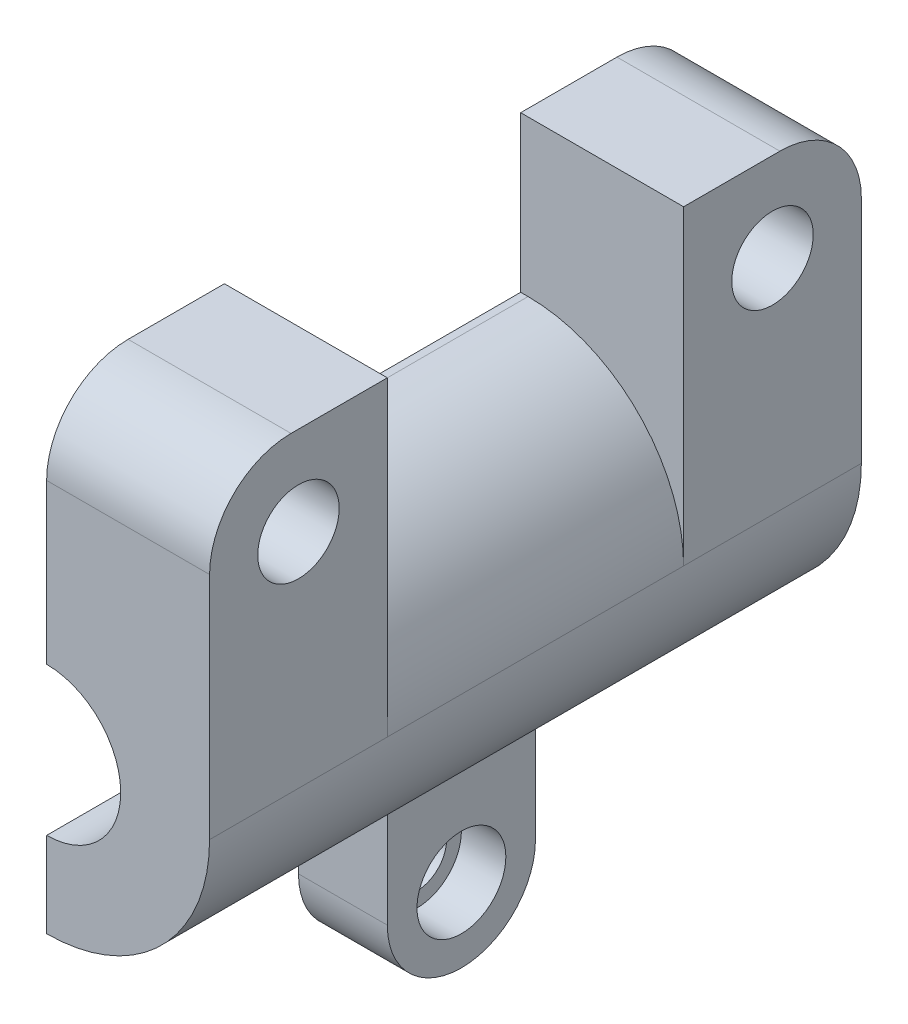
SolidWorks part; units mm, degrees
ref_plane "Front Plane" through (0, 0, 0) normal (0, 0, 1) x (1, 0, 0)
ref_plane "Top Plane" through (0, 0, 0) normal (0, 1, 0) x (1, 0, 0)
ref_plane "Right Plane" through (0, 0, 0) normal (1, 0, 0) x (0, 0, -1)
sketch "Sketch1" plane through (0, 0, 0) normal (1, 0, 0) x (0, 0, -1)
  line L1 (-22, -16) -> (22, -16)
  line L2 (-22, -16) -> (-22, 16)
  line L3 (-22, 16) -> (22, 16)
  line L4 (22, -16) -> (22, 16)
  line L5 (-22, -16) -> (22, 16) construction
  line L6 (-22, 16) -> (22, -16) construction
  point P0 (0, 0)
  dimension "D1" = 44
  dimension "D2" = 32
extrude "Boss-Extrude1" add sketch "Sketch1" along normal blind 11
sketch "Sketch2" plane through (0, 0, 0) normal (1, 0, 0) x (0, 0, -1)
  line L0 (-22, -16) -> (22, -16) construction
  line L1 (12.25, -13) -> (-12.25, -13)
  line L2 (12.25, -13) -> (12.25, 2.5)
  line L3 (12.25, 2.5) -> (-12.25, 2.5)
  line L4 (-12.25, -13) -> (-12.25, 2.5)
  line L5 (12.25, -13) -> (-12.25, 2.5) construction
  line L6 (12.25, 2.5) -> (-12.25, -13) construction
  point P0 (0, -5.25)
  dimension "D1" = 24.5
  dimension "D2" = 15.5
  dimension "D3" = 0
  dimension "D4" = 3
extrude "Cut-Extrude1" cut sketch "Sketch2" along normal blind 7.75 contours L2 L1 L4 L3
fillet "Fillet1" radius 7.75 2 edges at (7.75, 2.5, 0) (7.75, -13, 0)
sketch "Sketch3" plane through (0, 0, -12.25) normal (0, 0, 1) x (1, 0, 0)
  arc A0 (0, -13) -> (7.75, -5.25) centre (0, -5.25) ccw construction
  arc A1 (0, -13) -> (7.75, -5.25) centre (0, -5.25) ccw
  circle A2 centre (0, -5.25) radius 5
  line M3 (0, 2.5) -> (0, -13)
  dimension "D1" = 10
extrude "Cut-Extrude2" cut sketch "Sketch3" against normal through all both and the other way through all contours A2 M3 | A2 M3 region at (2.1221, -5.25, -12.25) region at (-2.1221, -5.25, -12.25)
sketch "Sketch4" plane through (11, 0, 0) normal (1, 0, 0) x (0, 0, -1)
  line L0 (22, 16) -> (-22, 16) construction
  line L2 (-10, 16) -> (10, 16)
  line L3 (-10, 16) -> (-10, 5.5)
  line L4 (-10, 5.5) -> (10, 5.5)
  line L5 (10, 16) -> (10, 5.5)
  circle A0 centre (-16, 10) radius 2.75
  circle A1 centre (16, 10) radius 2.75
  dimension "D1" = 5.5
  dimension "D2" = 5.5
  dimension "D3" = 6
  dimension "D4" = 6
  dimension "D5" = 6
  dimension "D6" = 6
  dimension "D7" = 32
  dimension "D8" = 10
  dimension "D9" = 10.5
extrude "Cut-Extrude3" cut sketch "Sketch4" against normal through all
sketch "Sketch5" plane through (11, 0, 0) normal (1, 0, 0) x (0, 0, -1)
  line L0 (-16, 10) -> (-16, 4.5)
  line L1 (-2.75, -3) -> (2.75, -3)
  line L2 (-2.75, -3) -> (-2.75, 0)
  line L3 (-2.75, 0) -> (2.75, 0)
  line L4 (2.75, -3) -> (2.75, 0)
  line L5 (-2.75, -3) -> (2.75, 0) construction
  line L6 (-2.75, 0) -> (2.75, -3) construction
  line L7 (16, 10) -> (16, 4.5)
  line L8 (-2.75, 0) -> (-16, 4.5)
  line L9 (2.75, 0) -> (16, 4.5)
  line L10 (2.75, -3) -> (16, 4.5)
  line L11 (-2.75, -3) -> (-16, 4.5)
  line L12 (16, 4.5) -> (16, -3)
  line L13 (16, -3) -> (2.75, -3)
  line L14 (-2.75, -3) -> (-16, -3)
  line L15 (-16, -3) -> (-16, 4.5)
  circle A0 centre (16, 10) radius 2.75 construction
  circle A1 centre (16, 10) radius 2.75
  circle A2 centre (-16, 10) radius 2.75 construction
  circle A3 centre (-16, 10) radius 2.75
  point P0 (0, -1.5)
  dimension "D1" = 10
  dimension "D2" = 3
  dimension "D3" = 5.5
  dimension "D4" = 0
  dimension "D5" = 5.5
  dimension "D6" = 5.5
extrude "Boss-Extrude4" [suppressed] add sketch "Sketch5" along normal blind 7 contours L15 L14 L11 | L11 L2 L8 | L1 L4 L3 L2 | L4 L10 L9 | L13 L12 L10
chamfer "Chamfer1" [suppressed] distance 7 angle 45
sketch "Sketch6" [suppressed] plane through (12, 0, 0) normal (1, 0, 0) x (0, 0, -1)
  line L0 (16, -3) -> (-16, -3) construction
  line L1 (16, -3) -> (-16, -3)
  line L2 (16, -10) -> (-16, -10) construction
  line L3 (-13, -3) -> (13, -3)
  line L4 (-13, -3) -> (-13, -10)
  line L5 (-13, -10) -> (13, -10)
  line L6 (13, -3) -> (13, -10)
  line L7 (-16, -10) -> (-16, -3) construction
  line L8 (10, 5.5) -> (-10, 5.5)
  line L9 (-10, 5.5) -> (-10, 16)
  line L10 (-10, 16) -> (-22, 16)
  line L11 (-22, 16) -> (-22, -16)
  line L12 (-22, -16) -> (22, -16)
  line L13 (22, -16) -> (22, 16)
  line L14 (22, 16) -> (10, 16)
  line L15 (10, 16) -> (10, 5.5)
  line L16 (10, 5.5) -> (-10, 5.5)
  line L17 (-10, 5.5) -> (-10, 16)
  line L18 (-10, 16) -> (-22, 16)
  line L19 (-22, 16) -> (-22, -16)
  line L20 (-22, -16) -> (22, -16)
  line L21 (22, -16) -> (22, 16)
  line L22 (22, 16) -> (10, 16)
  line L23 (10, 16) -> (10, 5.5)
  line L24 (16, 4.5) -> (16, -10) construction
  line L25 (-2.75, 0) -> (2.75, 0) construction
  line L26 (-1.5, -3) -> (1.5, -3)
  line L27 (-1.5, -3) -> (-1.5, -10)
  line L28 (-1.5, -10) -> (1.5, -10)
  line L29 (1.5, -3) -> (1.5, -10)
  point P26 (0, 0)
  line M13 (16, -10) -> (-16, -10)
  dimension "D2" = 3
  dimension "D3" = 3
  dimension "D4" = 3
  dimension "D5" = 1.5
  dimension "D1" = 0
extrude "Cut-Extrude5" [suppressed] cut sketch "Sketch6" along normal through all contours L27 L1 L4 L5 | L1 L29 L6 M13
fillet "Fillet4" radius 5.5 2 edges at (5.5, 16, -22) (5.5, 16, 22)
sketch "Sketch7" plane through (0, 0, 0) normal (1, 0, 0) x (0, 0, -1)
  line L0 (-22, -16) -> (22, -16) construction
  line L1 (5, -16) -> (-5, -16)
  line L2 (5, -16) -> (5, -26)
  line L3 (5, -26) -> (-5, -26)
  line L4 (-5, -16) -> (-5, -26)
  circle A0 centre (0, -21) radius 2
  dimension "D4" = 4
  dimension "D1" = 10
  dimension "D2" = 10
  dimension "D3" = 5
  dimension "D5" = 5
extrude "Boss-Extrude5" add sketch "Sketch7" along normal blind 6
sketch "Sketch8" plane through (6, 0, 0) normal (1, 0, 0) x (0, 0, -1)
  line L1 (0, -24.1754) -> (2.75, -22.5877)
  line L2 (2.75, -22.5877) -> (2.75, -19.4123)
  line L3 (2.75, -19.4123) -> (0, -17.8246)
  line L4 (0, -17.8246) -> (-2.75, -19.4123)
  line L5 (-2.75, -19.4123) -> (-2.75, -22.5877)
  line L6 (-2.75, -22.5877) -> (0, -24.1754)
  circle A0 centre (0, -21) radius 2 construction
  circle A1 centre (0, -21) radius 2
  circle A2 centre (0, -21) radius 2.75 construction
  dimension "D1" = 5.5
extrude "Cut-Extrude6" [suppressed] cut sketch "Sketch8" against normal blind 2
fillet "Fillet5" radius 5 2 edges at (3, -26, -5) (3, -26, 5)
sketch "Sketch9" plane through (6, 0, 0) normal (1, 0, 0) x (0, 0, -1)
  circle A0 centre (0, -21) radius 2 construction
  circle A1 centre (0, -21) radius 2
  circle A2 centre (0, -21) radius 3
  dimension "D1" = 6
extrude "Cut-Extrude7" cut sketch "Sketch9" against normal blind 3
sketch "Sketch10" plane through (11, 0, 0) normal (1, 0, 0) x (0, 0, -1)
  line L1 (-16, 5.3812) -> (-12, 7.6906)
  line L2 (-12, 7.6906) -> (-12, 12.3094)
  line L3 (-12, 12.3094) -> (-16, 14.6188)
  line L4 (-16, 14.6188) -> (-20, 12.3094)
  line L5 (-20, 12.3094) -> (-20, 7.6906)
  line L6 (-20, 7.6906) -> (-16, 5.3812)
  line L7 (16, 5.3812) -> (20, 7.6906)
  line L8 (20, 7.6906) -> (20, 12.3094)
  line L9 (20, 12.3094) -> (16, 14.6188)
  line L10 (16, 14.6188) -> (12, 12.3094)
  line L11 (12, 12.3094) -> (12, 7.6906)
  line L12 (12, 7.6906) -> (16, 5.3812)
  circle A0 centre (16, 10) radius 2.75 construction
  circle A1 centre (-16, 10) radius 2.75 construction
  circle A2 centre (16, 10) radius 2.75
  circle A3 centre (-16, 10) radius 2.75
  circle A4 centre (-16, 10) radius 4 construction
  circle A5 centre (16, 10) radius 4 construction
  dimension "D1" = 8
  dimension "D2" = 8
extrude "Cut-Extrude8" [suppressed] cut sketch "Sketch10" against normal blind 4
fillet "Fillet7" radius 10.5 1 edges at (11, 5.5, 0)
fillet "Fillet8" radius 11 1 edges at (11, -16, 0)
